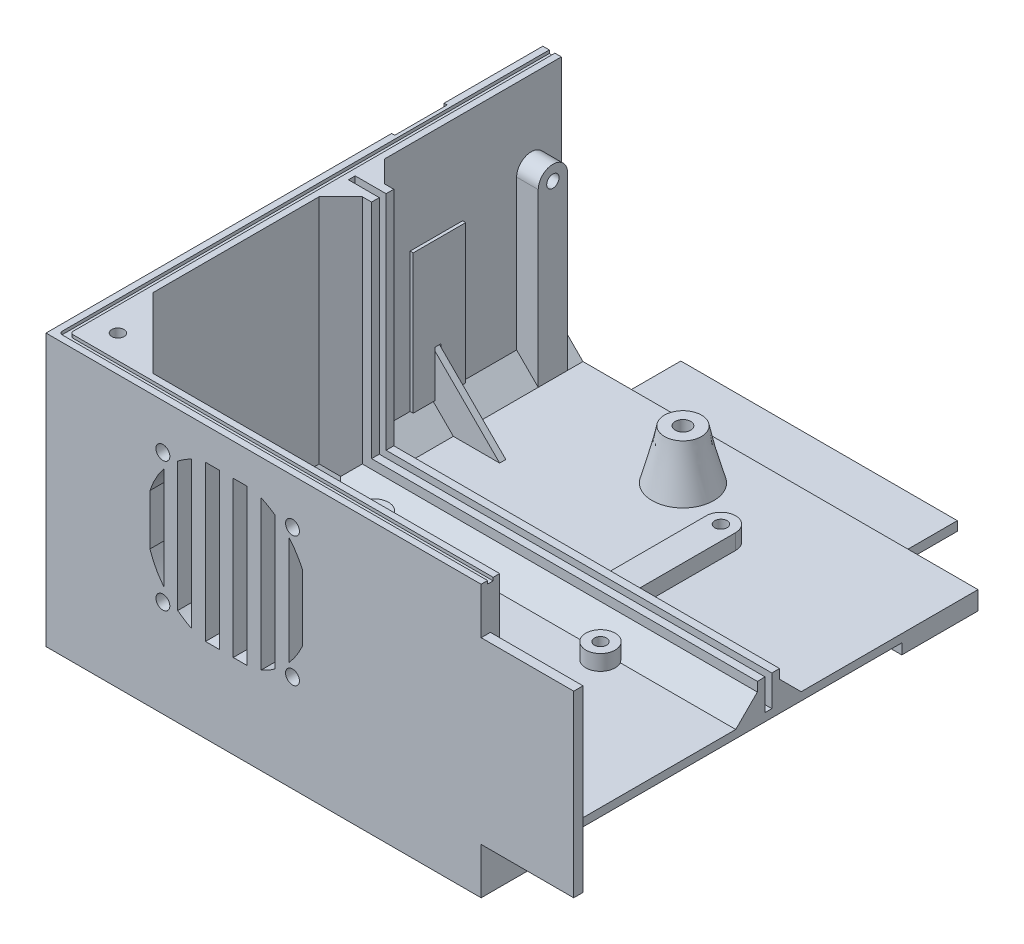
SolidWorks part; units mm, degrees
ref_plane "Front Plane" through (0, 0, 0) normal (0, 0, 1) x (1, 0, 0)
ref_plane "Top Plane" through (0, 0, 0) normal (0, 1, 0) x (1, 0, 0)
ref_plane "Right Plane" through (0, 0, 0) normal (1, 0, 0) x (0, 0, -1)
sketch "Sketch2" plane through (0, 0, 0) normal (0, 1, 0) x (1, 0, 0)
  line L1 (0, 0) -> (-141, 0)
  line L2 (0, 0) -> (0, -161)
  line L3 (0, -161) -> (-141, -161)
  line L4 (-141, 0) -> (-141, -161)
  dimension "D1" = 161
  dimension "D2" = 141
extrude "Boss-Extrude1" add sketch "Sketch2" along normal blind 88
sketch "Sketch3" plane through (0, 88, 0) normal (0, 1, 0) x (1, 0, 0)
  line L0 (-141, 0) -> (-141, -161) construction
  line L1 (0, 0) -> (-135, 0)
  line L2 (0, 0) -> (0, -155)
  line L3 (0, -155) -> (-135, -155)
  line L4 (-135, 0) -> (-135, -155)
  line L5 (-141, -161) -> (0, -161) construction
  dimension "D1" = 6
  dimension "D2" = 6
extrude "Cut-Extrude1" cut sketch "Sketch3" against normal blind 82
sketch "Sketch4" plane through (0, 0, 0) normal (0, -1, 0) x (1, 0, 0)
  line L0 (0, 161) -> (0, 0) construction
  line L1 (0, 136.3) -> (-41, 136.3)
  line L2 (0, 136.3) -> (0, 24.7)
  line L3 (0, 24.7) -> (-41, 24.7)
  line L4 (-41, 136.3) -> (-41, 24.7)
  line L5 (0, 0) -> (-141, 0) construction
  line L6 (-141, 161) -> (0, 161) construction
  dimension "D1" = 24.7
  dimension "D2" = 24.7
  dimension "D3" = 41
extrude "Cut-Extrude2" cut sketch "Sketch4" against normal blind 3.4
sketch "Sketch5" plane through (0, 0, 0) normal (0, -1, 0) x (1, 0, 0)
  line L0 (0, 0) -> (-141, 0) construction
  line L1 (-115.3, 0) -> (-25.7, 0)
  line L2 (-115.3, 0) -> (-115.3, -19)
  line L3 (-115.3, -19) -> (-25.7, -19)
  line L4 (-25.7, 0) -> (-25.7, -19)
  line L5 (-141, 0) -> (-141, 161) construction
  line L6 (0, 24.7) -> (0, 0) construction
  dimension "D1" = 25.7
  dimension "D2" = 25.7
  dimension "D3" = 19
extrude "Boss-Extrude2" add sketch "Sketch5" against normal blind 3
sketch "Sketch6" plane through (0, 0, 161) normal (0, 0, 1) x (1, 0, 0)
  line L0 (0, 88) -> (0, 0) construction
  line L1 (0, 15) -> (30, 15)
  line L2 (0, 15) -> (0, 73)
  line L3 (0, 73) -> (30, 73)
  line L4 (30, 15) -> (30, 73)
  line L5 (-141, 0) -> (0, 0) construction
  line L6 (-141, 88) -> (0, 88) construction
  dimension "D1" = 15
  dimension "D2" = 15
  dimension "D3" = 30
extrude "Boss-Extrude3" add sketch "Sketch6" against normal blind 3
sketch "Sketch7" plane through (-141, 0, 0) normal (-1, 0, 0) x (0, 0, 1)
  line L0 (0, 88) -> (0, 0) construction
  line L1 (0, 78.3) -> (9.4, 78.3)
  line L2 (0, 78.3) -> (0, 9.7)
  line L3 (0, 9.7) -> (9.4, 9.7)
  line L4 (9.4, 78.3) -> (9.4, 9.7)
  line L5 (0, 88) -> (161, 88) construction
  line L6 (0, 0) -> (161, 0) construction
  dimension "D1" = 9.7
  dimension "D2" = 9.7
  dimension "D3" = 9.4
extrude "Cut-Extrude3" cut sketch "Sketch7" against normal blind 3.4
sketch "Sketch8" plane through (0, 0, 161) normal (0, 0, 1) x (1, 0, 0)
  line L0 (-107.3246, 52.4335) -> (-56.9246, 52.4335)
  line L1 (-82.1246, 77.5835) -> (-82.1246, 27.2835) construction
  line L2 (-107.3246, 52.4335) -> (-56.9246, 52.4335) construction
  line L3 (-82.1246, 27.2835) -> (-82.1246, 77.5835)
  line L4 (-90.4749, 77.5835) -> (-73.7743, 77.5835)
  line L5 (-56.9246, 60.6316) -> (-56.9246, 44.2353)
  line L6 (-90.4749, 27.2835) -> (-73.7743, 27.2835)
  line L7 (-107.3246, 60.6316) -> (-107.3246, 44.2353)
  line L8 (-107.3246, 83.2191) -> (-107.3246, 12.2738)
  line L9 (-102.8246, 83.2191) -> (-102.8246, 12.2738)
  line L10 (-98.3246, 83.2191) -> (-98.3246, 12.2738)
  line L11 (-93.8246, 83.2191) -> (-93.8246, 12.2738)
  line L12 (-89.3246, 83.2191) -> (-89.3246, 12.2738)
  line L13 (-84.8246, 83.2191) -> (-84.8246, 12.2738)
  line L14 (-80.3246, 83.2191) -> (-80.3246, 12.2738)
  line L15 (-75.8246, 83.2191) -> (-75.8246, 12.2738)
  line L16 (-71.3246, 83.2191) -> (-71.3246, 12.2738)
  line L17 (-66.8246, 83.2191) -> (-66.8246, 12.2738)
  line L18 (-62.3246, 83.2191) -> (-62.3246, 12.2738)
  line L19 (-57.8246, 83.2191) -> (-57.8246, 12.2738)
  circle A0 centre (-103.1246, 73.4335) radius 2.25
  circle A1 centre (-61.1246, 73.4335) radius 2.25
  circle A2 centre (-61.1246, 31.4335) radius 2.25
  circle A3 centre (-103.1246, 31.4335) radius 2.25
  arc A4 (-107.3246, 44.2353) -> (-90.4749, 27.2835) centre (-82.1246, 52.4335) ccw
  arc A5 (-90.4749, 77.5835) -> (-107.3246, 60.6316) centre (-82.1246, 52.4335) ccw
  arc A6 (-73.7743, 27.2835) -> (-56.9246, 44.2353) centre (-82.1246, 52.4335) ccw
  arc A7 (-56.9246, 60.6316) -> (-73.7743, 77.5835) centre (-82.1246, 52.4335) ccw
  point P12 (-82.1246, 52.4335)
  point P15 (-82.1246, 52.4335)
  dimension "D1" = 4.5
  dimension "D2" = 42
  dimension "D3" = 50.4
extrude "Cut-Extrude4" cut sketch "Sketch8" against normal through all contours L9 A5 L7 L0 | L7 A4 L9 L0 | L10 A4 L11 L0 | L11 A5 L10 L0 | L13 L4 L12 L0 | L13 L0 L12 L6 | L15 L0 L14 L6 | L15 L4 L14 L0 | L17 A7 L16 L0 | L16 A6 L17 L0 | L18 A6 L19 L0 | L19 A7 L18 L0 | A0 | A3 | A2 | A1 region at (-104.8403, 59.1339, 161) region at (-104.8403, 45.733, 161) region at (-96.0279, 63.6875, 161) region at (-96.0279, 41.1794, 161) region at (-87.0746, 65.0085, 161) region at (-87.0746, 39.8585, 161) region at (-78.0746, 65.0085, 161) region at (-78.0746, 39.8585, 161) region at (-69.1162, 63.9531, 161) region at (-69.1162, 40.9139, 161) region at (-60.2535, 59.8236, 161) region at (-60.2535, 45.0433, 161)
sketch "Sketch9" plane through (-135, 0, 0) normal (1, 0, 0) x (0, 0, -1)
  line L0 (0, 88) -> (-155, 88) construction
  line L1 (-71.5, 88) -> (-69, 88)
  line L2 (-71.5, 88) -> (-71.5, 6)
  line L3 (-71.5, 6) -> (-69, 6)
  line L4 (-69, 88) -> (-69, 6)
  line L5 (0, 6) -> (-155, 6) construction
  line L7 (-155, 6) -> (-155, 88) construction
  line L8 (-66.8, 88) -> (-64.3, 88)
  line L9 (-66.8, 88) -> (-66.8, 6)
  line L10 (-66.8, 6) -> (-64.3, 6)
  line L11 (-64.3, 88) -> (-64.3, 6)
  dimension "D1" = 2.5
  dimension "D2" = 83.5
  dimension "D3" = 2.5
  dimension "D4" = 2.2
extrude "Boss-Extrude4" add sketch "Sketch9" along normal blind 10
sketch "Sketch10" plane through (0, 6, 0) normal (0, 1, 0) x (1, 0, 0)
  line L0 (0, -155) -> (0, 0) construction
  line L1 (-125, -69) -> (0, -69)
  line L2 (-125, -69) -> (-125, -71.5)
  line L3 (-125, -71.5) -> (0, -71.5)
  line L4 (0, -69) -> (0, -71.5)
  line L6 (-125, -64.3) -> (0, -64.3)
  line L7 (-125, -64.3) -> (-125, -66.8)
  line L8 (-125, -66.8) -> (0, -66.8)
  line L9 (0, -64.3) -> (0, -66.8)
  dimension "D1" = 2.5
  dimension "D2" = 2.5
extrude "Boss-Extrude5" add sketch "Sketch10" along normal blind 10
sketch "Sketch11" plane through (0, 88, 0) normal (0, 1, 0) x (1, 0, 0)
  line L0 (-135, -155) -> (-135, -132.3726)
  line L1 (-135, -71.5) -> (-135, -155) construction
  line L2 (-135, -132.3726) -> (-112.3726, -155)
  line L3 (-135, -155) -> (0, -155) construction
  line L4 (-112.3726, -155) -> (-135, -155)
  line L5 (-135, -155) -> (-123.6863, -143.6863) construction
  dimension "D2" = 16
extrude "Boss-Extrude6" add sketch "Sketch11" against normal blind 9
sketch "Sketch12" plane through (0, 88, 0) normal (0, 1, 0) x (1, 0, 0)
  line L0 (-123.6863, -143.6863) -> (-135, -155) construction
  line L1 (-112.3726, -155) -> (-135, -132.3726) construction
  line L2 (-112.3726, -155) -> (-135, -155) construction
  line L3 (-135, -155) -> (-135, -132.3726) construction
  circle A0 centre (-129.3431, -149.3431) radius 2
  dimension "D2" = 4
  dimension "D1" = 16
extrude "Cut-Extrude5" cut sketch "Sketch12" against normal blind 5
sketch "Sketch13" plane through (0, 6, 0) normal (0, 1, 0) x (1, 0, 0)
  line L0 (-135, -155) -> (-128, -155)
  line L1 (-135, -155) -> (0, -155) construction
  line L2 (-128, -155) -> (-135, -148)
  line L3 (-135, -71.5) -> (-135, -155) construction
  line L4 (-135, -148) -> (-135, -155)
  dimension "D1" = 7
extrude "Boss-Extrude7" add sketch "Sketch13" along normal up to surface (73 mm away) up to face at (-127.4575, 79, 147.4575)
sketch "Sketch14" plane through (0, 6, 0) normal (0, 1, 0) x (1, 0, 0)
  line L0 (0, -64.3) -> (-135, -64.3) construction
  line L1 (0, -64.3) -> (0, 0) construction
  line L2 (-59.75, -28.3) -> (-59.75, -64.3)
  line L3 (-59.75, -64.3) -> (-50.25, -64.3)
  line L4 (-50.25, -64.3) -> (-50.25, -28.3)
  arc A1 (-50.25, -28.3) -> (-59.75, -28.3) centre (-55, -28.3) ccw
  dimension "D2" = 9.5
  dimension "D5" = 36
  dimension "D7" = 55
extrude "Boss-Extrude8" add sketch "Sketch14" along normal blind 5
sketch "Sketch16" plane through (0, 11, 0) normal (0, 1, 0) x (1, 0, 0)
  circle A0 centre (-55, -28.3) radius 2
  dimension "D1" = 4
extrude "Cut-Extrude7" cut sketch "Sketch16" against normal blind 5
sketch "Sketch17" plane through (0, 6, 0) normal (0, 1, 0) x (1, 0, 0)
  line L0 (-135, -71.5) -> (-135, -78.5)
  line L1 (-135, -71.5) -> (-135, -148) construction
  line L2 (-135, -78.5) -> (-128, -71.5)
  line L3 (0, -71.5) -> (-135, -71.5) construction
  line L4 (-128, -71.5) -> (-135, -71.5)
  line L5 (-135, -64.3) -> (-135, -57.3)
  line L6 (-135, 0) -> (-135, -64.3) construction
  line L7 (-135, -57.3) -> (-128, -64.3)
  line L8 (0, -64.3) -> (-50.25, -64.3) construction
  line L9 (-128, -64.3) -> (-135, -64.3)
  dimension "D1" = 7
  dimension "D2" = 7
  dimension "D3" = 7
  dimension "D4" = 7
extrude "Boss-Extrude10" add sketch "Sketch17" along normal up to surface (82 mm away) up to face at (-129.3431, 88, 151.3431)
sketch "Sketch18" plane through (0, 6, 0) normal (0, 1, 0) x (1, 0, 0)
  line L0 (-125, -71.5) -> (0, -71.5) construction
  line L1 (-135, -78.5) -> (-135, -148) construction
  circle A0 centre (-115, -80.755) radius 4.75
  circle A1 centre (-41.57, -80.755) radius 4.75
  circle A2 centre (-115, -141.745) radius 4.75
  circle A3 centre (-41.57, -141.745) radius 4.75
  circle A4 centre (-115, -111.125) radius 4.75
  circle A5 centre (-115, -80.755) radius 2
  circle A6 centre (-115, -111.125) radius 2
  circle A7 centre (-115, -141.745) radius 2
  circle A8 centre (-41.57, -141.745) radius 2
  circle A9 centre (-41.57, -80.755) radius 2
  dimension "D2" = 9.5
  dimension "D3" = 4
  dimension "D1" = 73.43
  dimension "D4" = 30.37
  dimension "D5" = 60.99
  dimension "D6" = 9.255
  dimension "D7" = 20
extrude "Boss-Extrude11" add sketch "Sketch18" along normal blind 5
sketch "Sketch20" plane through (0, 0, 0) normal (1, 0, 0) x (0, 0, -1)
  line L0 (-71.5, 6) -> (-78.5, 6)
  line L1 (-155, 6) -> (-71.5, 6) construction
  line L2 (-78.5, 6) -> (-71.5, 13)
  line L3 (-71.5, 16) -> (-71.5, 6) construction
  line L4 (-71.5, 13) -> (-71.5, 6)
  dimension "D1" = 7
  dimension "D2" = 7
extrude "Boss-Extrude12" add sketch "Sketch20" against normal up to surface (135 mm away) up to face at (-135, 57.6667, 119.6242)
sketch "Sketch21" plane through (0, 0, 0) normal (1, 0, 0) x (0, 0, -1)
  line L0 (-64.3, 6) -> (-64.3, 13)
  line L1 (-64.3, 16) -> (-64.3, 6) construction
  line L2 (-64.3, 13) -> (-57.3, 6)
  line L3 (-64.3, 6) -> (0, 6) construction
  line L4 (-57.3, 6) -> (-64.3, 6)
  dimension "D1" = 7
  dimension "D2" = 7
extrude "Boss-Extrude13" add sketch "Sketch21" against normal up to surface (135 mm away) up to face at (-131.5, 47, 60.8)
sketch "Sketch22" plane through (0, 0, 0) normal (1, 0, 0) x (0, 0, -1)
  line L0 (-155, 6) -> (-155, 13)
  line L1 (-155, 6) -> (-155, 88) construction
  line L2 (-155, 13) -> (-148, 6)
  line L3 (-155, 6) -> (-78.5, 6) construction
  line L4 (-148, 6) -> (-155, 6)
  dimension "D1" = 7
  dimension "D2" = 7
extrude "Boss-Extrude14" add sketch "Sketch22" against normal up to surface (135 mm away) up to face at (-131.5, 42.5, 151.5)
sketch "Sketch23" plane through (0, 0, 161) normal (0, 0, 1) x (1, 0, 0)
  line L0 (-141, 0) -> (-141, 6) construction
  line L1 (-141, 88) -> (-141, 0) construction
  line L2 (-141, 6) -> (-135, 6) construction
  line L3 (-135, 6) -> (-135, 13)
  line L4 (-135, 13) -> (-128, 6)
  line L5 (-128, 6) -> (-135, 6)
  dimension "D1" = 6
  dimension "D2" = 7
extrude "Boss-Extrude15" add sketch "Sketch23" against normal up to surface (82.5 mm away) up to face at (-131.5, 48.75, 75)
sketch "Sketch24" plane through (0, 0, 0) normal (0, 0, -1) x (-1, 0, 0)
  line L0 (135, 6) -> (128, 6)
  line L1 (0, 6) -> (135, 6) construction
  line L2 (128, 6) -> (135, 13)
  line L3 (135, 6) -> (135, 88) construction
  line L4 (135, 13) -> (135, 6)
  dimension "D1" = 7
  dimension "D2" = 7
extrude "Boss-Extrude16" add sketch "Sketch24" against normal up to surface (57.3 mm away) up to face at (-131.5, 48.75, 60.8)
sketch "Sketch25" plane through (0, 6, 0) normal (0, 1, 0) x (1, 0, 0)
  line L1 (-135, -57.3) -> (-135, 0) construction
  line L2 (0, 0) -> (-128, 0) construction
  circle A0 centre (-77.77, -17.83) radius 10
  point P6 (-135, -28.65)
  dimension "D1" = 20
  dimension "D2" = 17.83
  dimension "D3" = 57.23
ref_plane "Plane1" through (0, 22, 0) normal (0, 1, 0) x (1, 0, 0)
sketch "Sketch28" plane through (0, 22, 0) normal (0, 1, 0) x (1, 0, 0)
  circle A0 centre (-77.77, -17.83) radius 10 construction
  circle A1 centre (-77.77, -17.83) radius 10 construction
  circle A2 centre (-77.77, -17.83) radius 6
  dimension "D1" = 12
loft "Loft1" add profiles "Sketch28", "Sketch25" connector at (-83.4752, 22, 19.6877) connector at (-85.0554, 6, 24.6801)
sketch "Sketch30" plane through (-135, 0, 0) normal (1, 0, 0) x (0, 0, -1)
  line L0 (0, 13) -> (0, 88) construction
  line L1 (0, 88) -> (-57.3, 88) construction
  circle A0 centre (-9.75, 61.5) radius 4.75
  dimension "D1" = 9.5
  dimension "D2" = 9.75
  dimension "D3" = 26.5
extrude "Boss-Extrude18" add sketch "Sketch30" along normal blind 7
sketch "Sketch31" plane through (-128, 0, 0) normal (1, 0, 0) x (0, 0, -1)
  circle A0 centre (-9.75, 61.5) radius 2
  dimension "D1" = 4
extrude "Cut-Extrude11" cut sketch "Sketch31" against normal blind 5
sketch "Sketch34" plane through (0, 22, 0) normal (0, 1, 0) x (1, 0, 0)
  circle A0 centre (-77.77, -17.83) radius 2.5
  circle A1 centre (-77.77, -17.83) radius 6 construction
  dimension "D1" = 5
extrude "Cut-Extrude13" cut sketch "Sketch34" against normal blind 6
sketch "Sketch36" plane through (0, 88, 0) normal (0, 1, 0) x (1, 0, 0)
  line L0 (-138.9, 0) -> (-138.9, -158.9)
  line L1 (-135, 0) -> (-141, 0) construction
  line L2 (-138.9, -158.9) -> (0, -158.9)
  line L3 (0, -161) -> (0, -155) construction
  line L4 (0, -158.9) -> (0, -157.1)
  line L5 (0, -157.1) -> (-137.1, -157.1)
  line L6 (-137.1, -157.1) -> (-137.1, 0)
  line L7 (-137.1, 0) -> (-138.9, 0)
  point P4 (0, -158)
  point P11 (0, -158)
  point P12 (-138, 0)
  point P13 (-138, 0)
  dimension "D1" = 1.8
  dimension "D2" = 1.8
extrude "Cut-Extrude14" cut sketch "Sketch36" against normal blind 1
sketch "Sketch37" plane through (-141, 0, 0) normal (-1, 0, 0) x (0, 0, 1)
  line L0 (0, 88) -> (161, 88) construction
  line L1 (30, 88) -> (60, 88)
  line L2 (30, 88) -> (30, 78)
  line L3 (30, 78) -> (60, 78)
  line L4 (60, 88) -> (60, 78)
  line L5 (0, 88) -> (0, 78.3) construction
  dimension "D1" = 30
  dimension "D2" = 10
  dimension "D3" = 30
extrude "Boss-Extrude19" [suppressed] add sketch "Sketch37" along normal blind 30
chamfer "Chamfer1" [suppressed] distance 10 distance2 15
sketch "Sketch38" plane through (-141, 0, 0) normal (-1, 0, 0) x (0, 0, 1)
  line L0 (0, 88) -> (161, 88) construction
  line L1 (0, 0) -> (161, 0) construction
  line L2 (32, 88) -> (49, 88)
  line L3 (32, 88) -> (32, 0)
  line L4 (32, 0) -> (49, 0)
  line L5 (49, 88) -> (49, 0)
  line L6 (161, 88) -> (161, 0) construction
  dimension "D1" = 17
  dimension "D2" = 112
extrude "Cut-Extrude15" cut sketch "Sketch38" against normal blind 1
ref_plane "Plane2" through (0, 0, 40) normal (0, 0, 1) x (1, 0, 0)
sketch "Sketch42" plane through (0, 0, 40) normal (0, 0, 1) x (1, 0, 0)
  line L0 (-135, 28) -> (-135, 13)
  line L1 (-135, 13) -> (-128, 6)
  line L2 (-128, 6) -> (-113, 6)
  line L3 (-113, 6) -> (-135, 28)
  line L4 (-135, 13) -> (-135, 88) construction
  line L5 (0, 6) -> (-128, 6) construction
  dimension "D1" = 15
extrude "Boss-Extrude21" add sketch "Sketch42" along normal blind 2
sketch "Sketch43" plane through (-128, 0, 0) normal (1, 0, 0) x (0, 0, -1)
  line L0 (-5, 6) -> (-5, 61.5)
  line L1 (-14.5, 6) -> (-14.5, 61.5)
  line L3 (-40, 6) -> (0, 6) construction
  line L5 (-14.5, 6) -> (-5, 6)
  circle A0 centre (-9.75, 61.5) radius 4.75 construction
  arc A1 (-14.5, 61.5) -> (-5, 61.5) centre (-9.75, 61.5) ccw
  dimension "D1" = 4.75
  dimension "D2" = 55.5
  dimension "D3" = 55.5
extrude "Boss-Extrude22" add sketch "Sketch43" against normal up to surface (7 mm away) up to face at (-135, 61.5, 14.5)
fillet "Fillet1" radius 1 2 edges at (-138.9, 87.5, 158.9) (-137.1, 87.5, 157.1)
sketch "Sketch44" plane through (-140, 0, 0) normal (-1, 0, 0) x (0, 0, 1)
  line L1 (49, 88) -> (32, 88) construction
  circle A0 centre (40.5, 48) radius 2
  point P5 (40.5, 88)
  dimension "D1" = 4
  dimension "D2" = 40
extrude "Cut-Extrude16" cut sketch "Sketch44" against normal blind 5
sketch "Sketch45" plane through (-135, 0, 0) normal (1, 0, 0) x (0, 0, -1)
  line L0 (-32, 88) -> (-32, 0) construction
  line L1 (-49, 0) -> (-49, 88) construction
  line L2 (-32, 58) -> (-32, 13)
  line L3 (-49, 13) -> (-49, 58)
  line L4 (-42, 13) -> (-49, 13)
  line L5 (-57.3, 13) -> (-42, 13) construction
  line L6 (-42, 13) -> (-42, 28)
  line L7 (-42, 28) -> (-40, 28)
  line L8 (-40, 28) -> (-40, 13)
  line L9 (-40, 13) -> (-32, 13)
  line L10 (-40, 13) -> (-14.5, 13) construction
  line L11 (-49, 58) -> (-32, 58)
  line L12 (0, 88) -> (-57.3, 88) construction
  dimension "D1" = 30
extrude "Boss-Extrude23" add sketch "Sketch45" along normal blind 1
